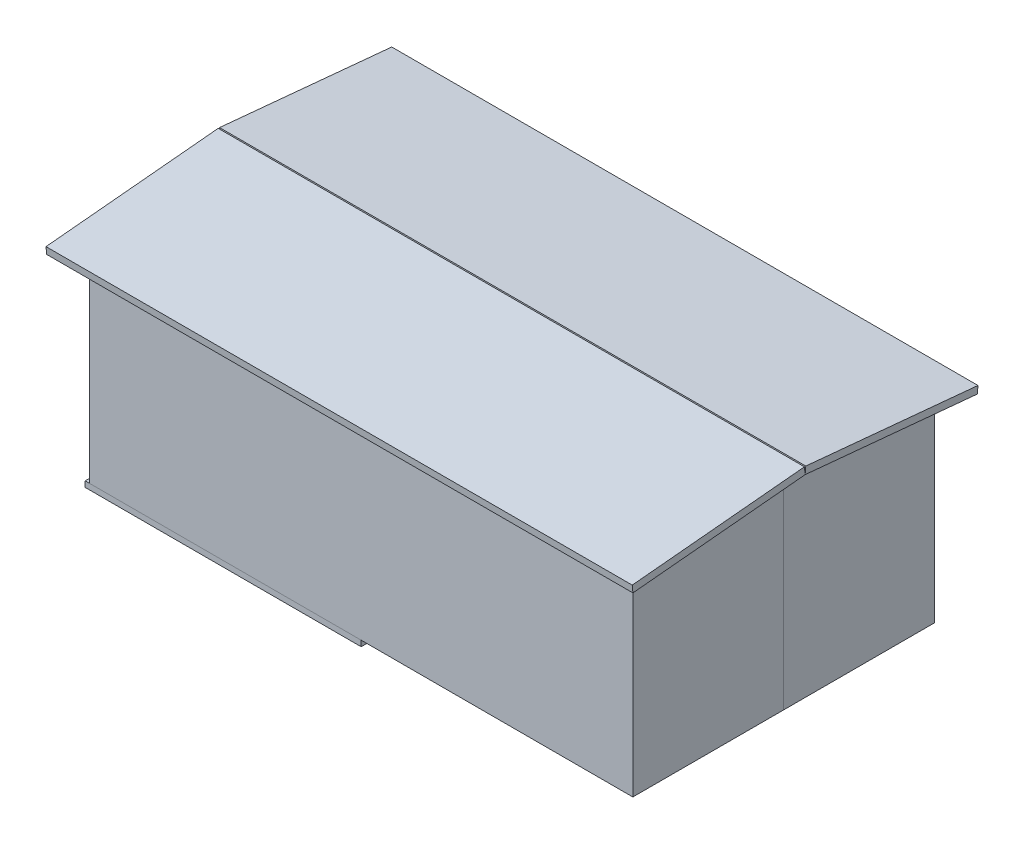
SolidWorks part; units mm, degrees
ref_plane "Front Plane" through (0, 0, 0) normal (0, 0, 1) x (1, 0, 0)
ref_plane "Top Plane" through (0, 0, 0) normal (0, 1, 0) x (1, 0, 0)
ref_plane "Right Plane" through (0, 0, 0) normal (1, 0, 0) x (0, 0, -1)
other "Configuration Table"
sketch "MetalBase" plane through (0, 0, 0) normal (0, 1, 0) x (1, 0, 0)
  line L0 (-60, -60) -> (7660, -60)
  line L1 (0, 0) -> (7600, 0)
  line L2 (0, 0) -> (0, 2020)
  line L3 (0, 4100) -> (7600, 4100)
  line L4 (7600, 0) -> (7600, 2020)
  line L5 (7660, -60) -> (7660, 4160)
  line L6 (-60, 4160) -> (7660, 4160)
  line L7 (-60, -60) -> (-60, 4160)
  line L8 (0, 2050) -> (7600, 2050) construction
  line L9 (0, 2020) -> (7600, 2020)
  line L10 (0, 2080) -> (7600, 2080)
  line L11 (0, 2080) -> (0, 4100)
  line L12 (7600, 2080) -> (7600, 4100)
  line L13 (0, 0) -> (0, 4100) construction
  line L15 (7600, 0) -> (7600, 4100) construction
  point P15 (7660, 2050)
  dimension "D1" = 4100
  dimension "D2" = 7600
  dimension "D6" = 4220
  dimension "D7" = 7720
  dimension "D3" = 60
  dimension "D4" = 30
  dimension "D5" = 30
sketch "InternalSpace" plane through (0, 0, 0) normal (0, 1, 0) x (1, 0, 0)
  line L26 (50, 50) -> (7550, 50)
  line L27 (7550, 50) -> (7550, 4050)
  line L28 (7550, 4050) -> (50, 4050)
  line L29 (50, 4050) -> (50, 50)
  line L30 (50, 50) -> (7550, 50)
  line L31 (7550, 50) -> (7550, 4050)
  line L32 (7550, 4050) -> (50, 4050)
  line L33 (50, 4050) -> (50, 50)
  dimension "D2" = 4000
  dimension "D3" = 7500
  dimension "D1" = 110
sketch "Furniture" plane through (0, 0, 0) normal (0, 1, 0) x (1, 0, 0)
  line L0 (6750, 2050) -> (6750, 4050)
  line L1 (2200, 2550) -> (1400, 2550)
  line L2 (2200, 2550) -> (2200, 4050)
  line L3 (2200, 4050) -> (1400, 4050)
  line L4 (1400, 2550) -> (1400, 4050)
  line L5 (1050, 50) -> (50, 50)
  line L6 (1050, 50) -> (1050, 2050)
  line L7 (1050, 2050) -> (50, 2050)
  line L8 (50, 50) -> (50, 2050)
  line L9 (6350, 2110) -> (7550, 2110)
  line L10 (2200, 4050) -> (2200, 150)
  line L11 (0, 0) -> (7600, 0) construction
  line L12 (6350, 50) -> (6350, 2110)
  line L13 (6470, 50) -> (6470, 1990)
  line L15 (2200, 2050) -> (7550, 2050) construction
  line L17 (1979.5569, 919.0285) -> (2200, 150)
  line L18 (6350, 150) -> (5722.0427, 459.305)
  line L19 (6710, 1120.0467) -> (7310, 1120.0467)
  line L24 (6710, 1120.0467) -> (6710, 1880.0467)
  line L25 (6710, 1880.0467) -> (7310, 1880.0467)
  line L26 (7310, 1120.0467) -> (7310, 1880.0467)
  line L27 (6350, 2110) -> (5750, 2110)
  line L28 (6350, 2110) -> (6350, 1510)
  line L29 (6350, 1510) -> (5750, 1510)
  line L30 (5750, 2110) -> (5750, 1510)
  line L31 (2320, 2050) -> (4320, 2050) construction
  line L32 (4320, 2050) -> (4320, 4050) construction
  line L33 (2200, 150) -> (2499.3532, 150) construction
  line L34 (2499.3532, 150) -> (2499.3532, 981.1813) construction
  line L35 (2499.3532, 981.1813) -> (2200, 981.1813) construction
  line L36 (2320, 4050) -> (2320, 150)
  line L37 (2200, 150) -> (2200, 50)
  line L38 (50, 50) -> (7550, 50) construction
  line L39 (2320, 150) -> (2320, 50)
  line L40 (7550, 4050) -> (50, 4050) construction
  line L41 (7550, 50) -> (7550, 4050) construction
  line L42 (50, 4050) -> (50, 50) construction
  line L43 (7550, 4050) -> (50, 4050) construction
  line L44 (7550, 50) -> (7550, 4050) construction
  line L45 (50, 50) -> (7550, 50) construction
  line L46 (50, 4050) -> (50, 50) construction
  line L47 (7010, 1120.0467) -> (7010, 1445.9123) construction
  line L48 (6470, 1990) -> (7550, 1990)
  line L49 (-60, -60) -> (-60, 4160) construction
  line L50 (7550, 809.8905) -> (7383.7397, 809.8905)
  line L51 (7550, 809.8905) -> (7550, 230.8186)
  line L52 (7550, 230.8186) -> (7383.7397, 230.8186)
  line L53 (7283.7397, 709.8905) -> (7283.7397, 330.8186)
  line L54 (7660, 4160) -> (-60, 4160) construction
  line L55 (-60, 4160) -> (-60, -60) construction
  line L56 (-60, -60) -> (7660, -60) construction
  line L57 (7660, -60) -> (7660, 4160) construction
  arc A1 (1979.5569, 919.0285) -> (1414.1883, 0) centre (2200, 150) ccw construction
  arc A2 (5722.0427, 459.305) -> (6350, 850) centre (6350, 150) cw construction
  arc A3 (7383.7397, 230.8186) -> (7283.7397, 330.8186) centre (7383.7397, 330.8186) cw
  arc A4 (7383.7397, 809.8905) -> (7283.7397, 709.8905) centre (7383.7397, 709.8905) ccw
  point P56 (7010, 1990)
  dimension "D13" = 600
  dimension "D21" = 100
  dimension "D1" = 1500
  dimension "D2" = 800
  dimension "D3" = 2000
  dimension "D4" = 1000
  dimension "D5" = 100
  dimension "D6" = 60
  dimension "D7" = 700
  dimension "D8" = 600
  dimension "D9" = 2260
  dimension "D10" = 800
  dimension "D11" = 100
  dimension "D12" = 760
  dimension "D14" = 2000
  dimension "D15" = 800
  dimension "D16" = 2000
  dimension "D17" = 600
  dimension "D18" = 60
  dimension "D19" = 4150
  dimension "D20" = 120
  dimension "D22" = 120
  dimension "D23" = 110
  dimension "D25" = 4220
  dimension "D26" = 1200
  dimension "D27" = 4030
  dimension "D24" = 110
sketch "Metal frame" plane through (0, 0, 0) normal (0, 1, 0) x (1, 0, 0)
  line L0 (0, 4100) -> (7600, 4100) construction
  line L1 (0, 4100) -> (7600, 4100)
  line L3 (0, 0) -> (0, 2020)
  line L4 (0, 0) -> (7600, 0) construction
  line L5 (0, 0) -> (7600, 0)
  line L7 (7600, 0) -> (7600, 2020)
  line L8 (-60, 4160) -> (7660, 4160)
  line L9 (7660, -60) -> (7660, 4160)
  line L10 (-60, -60) -> (7660, -60)
  line L11 (-60, -60) -> (-60, 4160)
  line L12 (0, 2050) -> (62.1159, 2050) construction
  line L13 (7600, 2080) -> (0, 2080)
  line L15 (7600, 2020) -> (0, 2020)
  line L17 (7600, 2080) -> (7600, 4100)
  line L18 (0, 2080) -> (0, 4100)
  line L19 (7600, 0) -> (7600, 4100) construction
  line L21 (0, 0) -> (0, 4100) construction
  point P14 (-60, 2050)
  dimension "D2" = 7720
  dimension "D3" = 4220
  dimension "D4" = 60
  dimension "D1" = 60
sketch "Walls bottom" plane through (0, 0, 0) normal (0, 1, 0) x (1, 0, 0)
  line L0 (-60, 4160) -> (7660, 4160) construction
  line L2 (-60, -60) -> (7660, -60) construction
  line L3 (7660, -60) -> (7660, 4160) construction
  line L4 (-60, -60) -> (-60, 4160) construction
  line L5 (-60, -60) -> (7660, -60)
  line L6 (7660, -60) -> (7660, 4160)
  line L7 (-60, 4160) -> (7660, 4160)
  line L8 (-60, -60) -> (-60, 4160)
  line L9 (40, 40) -> (40, 4060)
  line L10 (40, 4060) -> (7560, 4060)
  line L11 (7560, 40) -> (7560, 4060)
  line L12 (40, 40) -> (7560, 40)
  dimension "D2" = 4020
  dimension "D3" = 7520
  dimension "D4" = 7720
  dimension "D5" = 4220
  dimension "D1" = 100
sketch "Sketch15" plane through (0, 0, 0) normal (0, 1, 0) x (1, 0, 0)
  line L2 (7550, 50) -> (5502.4266, 50)
  line L3 (7550, 50) -> (7550, 1250)
  line L4 (7550, 1250) -> (5502.4266, 1250)
  line L5 (5502.4266, 50) -> (5502.4266, 1250)
  dimension "D1" = 1200
extrude "MetalFrame" add sketch "Metal frame" against normal blind 80 contours L11 L10 L9 L8 L15 L7 L5 L3 L13 L18 L1 L17 region at (3800, 0, -2050)
sketch "Sketch18" plane through (0, 0, 0) normal (0, 1, 0) x (1, 0, 0)
  line L0 (0, 0) -> (7600, 0) construction
  line L1 (3800, -1014.8769) -> (8467.9433, -1014.8769)
  line L2 (3800, -1014.8769) -> (3800, 5493.3133)
  line L3 (3800, 5493.3133) -> (8467.9433, 5493.3133)
  line L4 (8467.9433, -1014.8769) -> (8467.9433, 5493.3133)
  point P6 (3800, 0)
extrude "Cut-Extrude1" cut sketch "Sketch18" against normal through all
sketch "Sketch19" plane through (0, 0, 0) normal (0, 1, 0) x (1, 0, 0)
  line L0 (0, 0) -> (3800, 0) construction
  line L1 (3800, 4100) -> (3740, 4100)
  line L2 (3800, 4100) -> (3800, 0)
  line L3 (3800, 0) -> (3740, 0)
  line L4 (3740, 4100) -> (3740, 0)
  dimension "D1" = 60
extrude "Boss-Extrude1" add sketch "Sketch19" against normal blind 80
sketch "Sketch20" plane through (0, 0, 0) normal (1, 0, 0) x (0, 0, -1)
  line L0 (2050, 0) -> (2050, 3000) construction
  line L1 (4160, 0) -> (-60, 0) construction
  line L2 (4160, 0) -> (4160, 2800) construction
  line L3 (4160, 2800) -> (2050, 3000) construction
  line L4 (2050, 3000) -> (5424.8088, 3000) construction
  line L5 (4160, 2800) -> (4439.2907, 2773.5269) construction
  line L6 (4160, 150) -> (-211.81, 150) construction
  dimension "D1" = 2650
  dimension "D2" = 3000
  dimension "D3" = 150
  dimension "D4" = 2119.4575
  dimension "D5" = 2400
  dimension "D6" = 280.5425
  dimension "D7" = 2800
  dimension "D8" = 5.415
sketch "Sketch21" plane through (0, 0, 0) normal (1, 0, 0) x (0, 0, -1)
  line L0 (2050, 0) -> (4160, 0)
  line L1 (4160, 0) -> (4160, 2800)
  line L2 (4160, 2800) -> (2050, 3000)
  line L3 (2050, 3000) -> (2050, 0)
extrude "Boss-Extrude3" add sketch "Sketch21" along normal blind 7600 separate body
sketch "Sketch22" plane through (0, 3165.869, -300.0824) normal (0, 0.9955, -0.0944) x (1, 0, 0)
  line L1 (-300, 1757.7611) -> (7900, 1757.7611)
  line L2 (-300, 1757.7611) -> (-300, 4177.2186)
  line L3 (-300, 4177.2186) -> (7900, 4177.2186)
  line L4 (7900, 1757.7611) -> (7900, 4177.2186)
  line M2 (0, 3877.2186) -> (0, 1757.7611)
  line M3 (0, 1757.7611) -> (7600, 1757.7611)
  line M4 (7600, 1757.7611) -> (7600, 3877.2186)
  line M5 (7600, 3877.2186) -> (0, 3877.2186)
  dimension "D1" = 300
  dimension "D2" = 300
  dimension "D3" = 300
extrude "Boss-Extrude4" add sketch "Sketch22" along normal blind 100 separate body contours L1 L4 L3 L2 M2 M5 M4 | M5 M2 M3 M4 region at (-214.5051, 2885.8454, -3254.3307) region at (3800, 2900, -3105)
mirror "Mirror1" about plane through (7600, 3000, -2050) normal (0, 0, -1) of bodies 332 331
